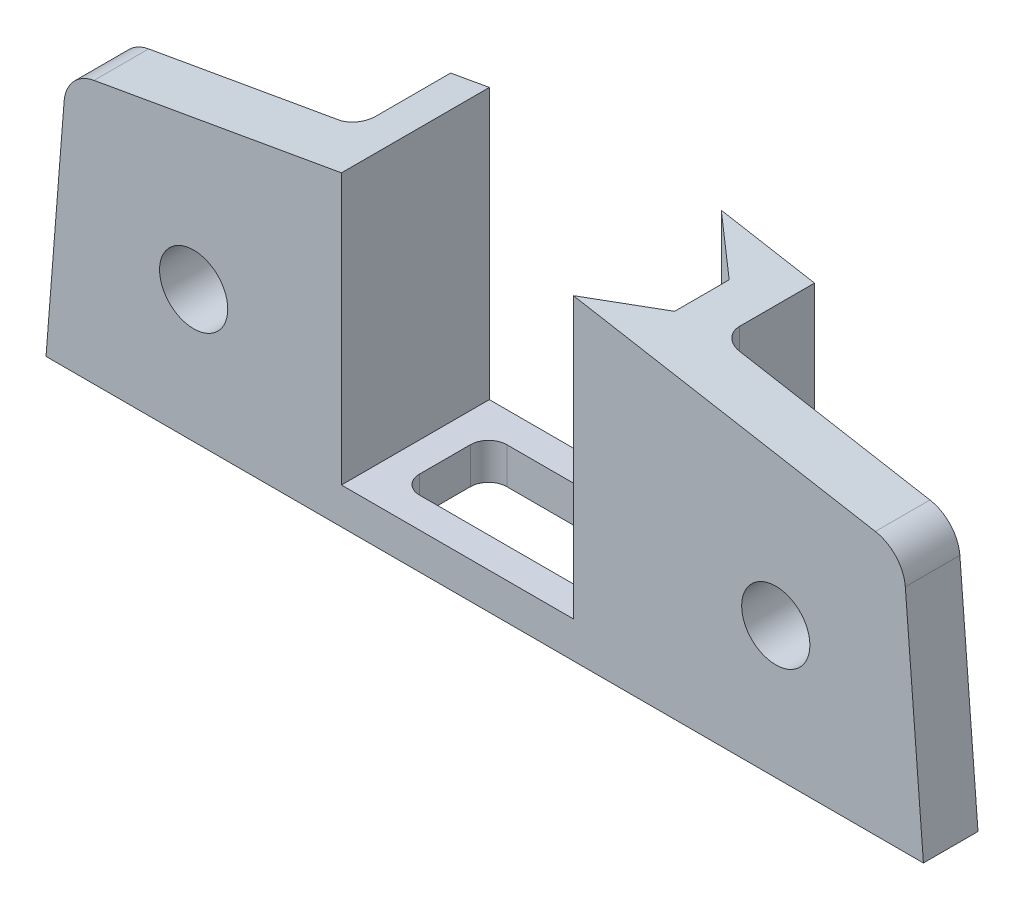
SolidWorks part; units mm, degrees
ref_plane "Front Plane" through (0, 0, 0) normal (0, 0, 1) x (1, 0, 0)
ref_plane "Top Plane" through (0, 0, 0) normal (0, 1, 0) x (1, 0, 0)
ref_plane "Right Plane" through (0, 0, 0) normal (1, 0, 0) x (0, 0, -1)
sketch "Sketch1" plane through (0, 0, 0) normal (0, 0, 1) x (1, 0, 0)
  line L0 (-24.457, 69.4319) -> (24.457, 69.4319)
  line L18 (24.457, 69.4319) -> (23.1215, 86.4007)
  line L19 (21.475, 88.2134) -> (0, 92)
  line L20 (0, 92) -> (-21.475, 88.2134)
  line L21 (-23.1215, 86.4007) -> (-24.457, 69.4319)
  line L22 (-24.5714, 68.9048) -> (-33.6515, 43.9576)
  line L23 (-33.4302, 42.1552) -> (-25.3419, 30.1639)
  line L24 (-25, 29.0455) -> (-25, -29.0455)
  line L25 (-25.3419, -30.1639) -> (-33.4302, -42.1552)
  line L26 (-33.6515, -43.9576) -> (-24.5714, -68.9048)
  line L27 (-24.457, -69.4319) -> (-23.1215, -86.4007)
  line L28 (-21.475, -88.2134) -> (0, -92)
  line L29 (0, -92) -> (21.475, -88.2134)
  line L30 (23.1215, -86.4007) -> (24.457, -69.4319)
  line L31 (24.5714, -68.9048) -> (33.6515, -43.9576)
  line L32 (33.4302, -42.1552) -> (25.3419, -30.1639)
  line L33 (25, -29.0455) -> (25, 29.0455)
  line L34 (25.3419, 30.1639) -> (33.4302, 42.1552)
  line L35 (33.6515, 43.9576) -> (24.5714, 68.9048)
  line L36 (24.457, 69.4319) -> (23.1215, 86.4007)
  line L37 (21.475, 88.2134) -> (0, 92)
  line L38 (0, 92) -> (-21.475, 88.2134)
  line L39 (-23.1215, 86.4007) -> (-24.457, 69.4319)
  circle A0 centre (-16, 81) radius 1.5 construction
  circle A1 centre (-16, 81) radius 1.5
  circle A2 centre (16, 81) radius 1.5 construction
  circle A3 centre (16, 81) radius 1.5
  arc A16 (24.457, 69.4319) -> (24.5714, 68.9048) centre (26.4508, 69.5889) ccw
  arc A17 (23.1215, 86.4007) -> (21.475, 88.2134) centre (21.1277, 86.2438) ccw
  arc A18 (-21.475, 88.2134) -> (-23.1215, 86.4007) centre (-21.1277, 86.2438) ccw
  arc A19 (-24.5714, 68.9048) -> (-24.457, 69.4319) centre (-26.4508, 69.5889) ccw
  arc A20 (-33.6515, 43.9576) -> (-33.4302, 42.1552) centre (-31.7721, 43.2736) ccw
  arc A21 (-25, 29.0455) -> (-25.3419, 30.1639) centre (-27, 29.0455) ccw
  arc A22 (-25.3419, -30.1639) -> (-25, -29.0455) centre (-27, -29.0455) ccw
  arc A23 (-33.4302, -42.1552) -> (-33.6515, -43.9576) centre (-31.7721, -43.2736) ccw
  arc A24 (-24.457, -69.4319) -> (-24.5714, -68.9048) centre (-26.4508, -69.5889) ccw
  arc A25 (-23.1215, -86.4007) -> (-21.475, -88.2134) centre (-21.1277, -86.2438) ccw
  arc A26 (21.475, -88.2134) -> (23.1215, -86.4007) centre (21.1277, -86.2438) ccw
  arc A27 (24.5714, -68.9048) -> (24.457, -69.4319) centre (26.4508, -69.5889) ccw
  arc A28 (33.6515, -43.9576) -> (33.4302, -42.1552) centre (31.7721, -43.2736) ccw
  arc A29 (25, -29.0455) -> (25.3419, -30.1639) centre (27, -29.0455) ccw
  arc A30 (25.3419, 30.1639) -> (25, 29.0455) centre (27, 29.0455) ccw
  arc A31 (33.4302, 42.1552) -> (33.6515, 43.9576) centre (31.7721, 43.2736) ccw
  arc A33 (23.1215, 86.4007) -> (21.475, 88.2134) centre (21.1277, 86.2438) ccw
  arc A34 (-21.475, 88.2134) -> (-23.1215, 86.4007) centre (-21.1277, 86.2438) ccw
  dimension "D1" = 0
extrude "Boss-Extrude1" add sketch "Sketch1" along normal blind 8.13
ref_plane "Plane1" through (0, 92, 0) normal (0, 1, 0) x (1, 0, 0)
sketch "Sketch2" plane through (0, 92, 0) normal (0, 1, 0) x (1, 0, 0)
  line L0 (0, -4.065) -> (24.457, -4.065) construction
  line L1 (0, -8.13) -> (0, 0) construction
  line L2 (24.457, -8.13) -> (24.457, 0) construction
  line L3 (21.475, -8.13) -> (0, -8.13) construction
  line L4 (-7.875, 0) -> (7.875, 0)
  line L5 (-7.875, 0) -> (-7.875, -8.13)
  line L6 (-7.875, -8.13) -> (7.875, -8.13)
  line L7 (7.875, 0) -> (7.875, -8.13)
  line L8 (-7.875, 0) -> (7.875, -8.13) construction
  line L9 (-7.875, -8.13) -> (7.875, 0) construction
  line L10 (7.875, -2.565) -> (4.875, 0)
  line L11 (7.875, -5.565) -> (4.875, -8.13)
  dimension "D1" = 15.75
  dimension "D2" = 12.75
  dimension "D3" = 3
extrude "Cut-Extrude1" cut sketch "Sketch2" against normal blind 16.25 contours L11 L7 L10 L4 L5 L6 region at (-0.4396, 92, 4.065)
sketch "Sketch3" plane through (0, 75.75, 0) normal (0, 1, 0) x (1, 0, 0)
  line L0 (0, 0) -> (0, -8.13) construction
  line L1 (-7.875, -8.13) -> (4.875, -8.13) construction
  line L2 (0, -4.065) -> (24.457, -4.065) construction
  line L3 (24.457, -8.13) -> (24.457, 0) construction
  line L5 (-6.25, -1.665) -> (6.25, -1.665)
  line L6 (-6.25, -1.665) -> (-6.25, -6.465)
  line L7 (-6.25, -6.465) -> (6.25, -6.465)
  line L8 (6.25, -1.665) -> (6.25, -6.465)
  line L9 (-6.25, -1.665) -> (6.25, -6.465) construction
  line L10 (-6.25, -6.465) -> (6.25, -1.665) construction
  dimension "D1" = 12.5
  dimension "D2" = 4.8
extrude "Cut-Extrude2" cut sketch "Sketch3" against normal up to next
sketch "Sketch4" plane through (0, 0, 0) normal (0, 0, -1) x (-1, 0, 0)
  line L0 (-10, 90.2367) -> (-10, 69.4319)
  line L1 (0, 69.4319) -> (0, 91.1404) construction
  line L2 (10, 90.2367) -> (10, 69.4319)
  line L8 (21.475, 88.2134) -> (7.875, 90.6114)
  line L9 (7.875, 90.6114) -> (7.875, 75.75)
  line L10 (7.875, 75.75) -> (-4.875, 75.75)
  line L11 (-4.875, 75.75) -> (-4.875, 91.1404)
  line L12 (-4.875, 91.1404) -> (-21.475, 88.2134)
  line L13 (-23.1215, 86.4007) -> (-24.457, 69.4319)
  line L14 (-24.457, 69.4319) -> (24.457, 69.4319)
  line L15 (24.457, 69.4319) -> (23.1215, 86.4007)
  line L16 (21.475, 88.2134) -> (7.875, 90.6114)
  line L17 (7.875, 90.6114) -> (7.875, 75.75)
  line L18 (7.875, 75.75) -> (-4.875, 75.75)
  line L19 (-4.875, 75.75) -> (-4.875, 91.1404)
  line L20 (-4.875, 91.1404) -> (-21.475, 88.2134)
  line L21 (-23.1215, 86.4007) -> (-24.457, 69.4319)
  line L22 (-24.457, 69.4319) -> (24.457, 69.4319)
  line L23 (24.457, 69.4319) -> (23.1215, 86.4007)
  arc A2 (-21.475, 88.2134) -> (-23.1215, 86.4007) centre (-21.1277, 86.2438) ccw
  arc A3 (23.1215, 86.4007) -> (21.475, 88.2134) centre (21.1277, 86.2438) ccw
  arc A4 (-21.475, 88.2134) -> (-23.1215, 86.4007) centre (-21.1277, 86.2438) ccw
  arc A5 (23.1215, 86.4007) -> (21.475, 88.2134) centre (21.1277, 86.2438) ccw
  line M11 (21.475, 88.2134) -> (7.875, 90.6114)
  line M15 (-4.875, 91.1404) -> (-21.475, 88.2134)
  arc M16 (-21.475, 88.2134) -> (-23.1215, 86.4007) centre (-21.1277, 86.2438) ccw
  line M17 (-23.1215, 86.4007) -> (-24.457, 69.4319)
  line M18 (-24.457, 69.4319) -> (24.457, 69.4319)
  line M19 (24.457, 69.4319) -> (23.1215, 86.4007)
  arc M20 (23.1215, 86.4007) -> (21.475, 88.2134) centre (21.1277, 86.2438) ccw
  circle M21 centre (16, 81) radius 1.5
  circle M22 centre (-16, 81) radius 1.5
  dimension "D2" = 10
  dimension "D1" = 0
extrude "Cut-Extrude3" cut sketch "Sketch4" against normal offset from surface (5.13 mm away) 3 contours L0 M15 M16 M17 M18 M22 | L2 M11 M18 M19 M20 M21 region at (16.7394, 79.0217, 0) region at (-16.7394, 79.0217, 0) up to face at (17.5, 81, 8.13)
sketch "Sketch5" plane through (0, 0, 0) normal (0, 0, -1) x (-1, 0, 0)
  line L1 (7.875, 75.75) -> (-4.875, 75.75) construction
  line L2 (-24.457, 69.4319) -> (24.457, 69.4319)
  line L3 (-24.457, 69.4319) -> (-24.457, 73.75)
  line L4 (-24.457, 73.75) -> (24.457, 73.75)
  line L6 (24.457, 69.4319) -> (24.457, 73.75)
  dimension "D1" = 2
extrude "Cut-Extrude4" cut sketch "Sketch5" against normal up to next
fillet "Fillet1" radius 1 6 edges at (-6.25, 74.75, 1.665) (6.25, 74.75, 1.665) (6.25, 74.75, 6.465) (-6.25, 74.75, 6.465) (-10, 81.9934, 5.13) (10, 81.9934, 5.13)
sketch "Sketch8" plane through (0, 0, 5.13) normal (0, 0, -1) x (-1, 0, 0)
  circle A0 centre (16, 81) radius 1.875
  circle A1 centre (-16, 81) radius 1.875
  dimension "D1" = 3.75
extrude "Cut-Extrude6" cut sketch "Sketch8" against normal up to next
